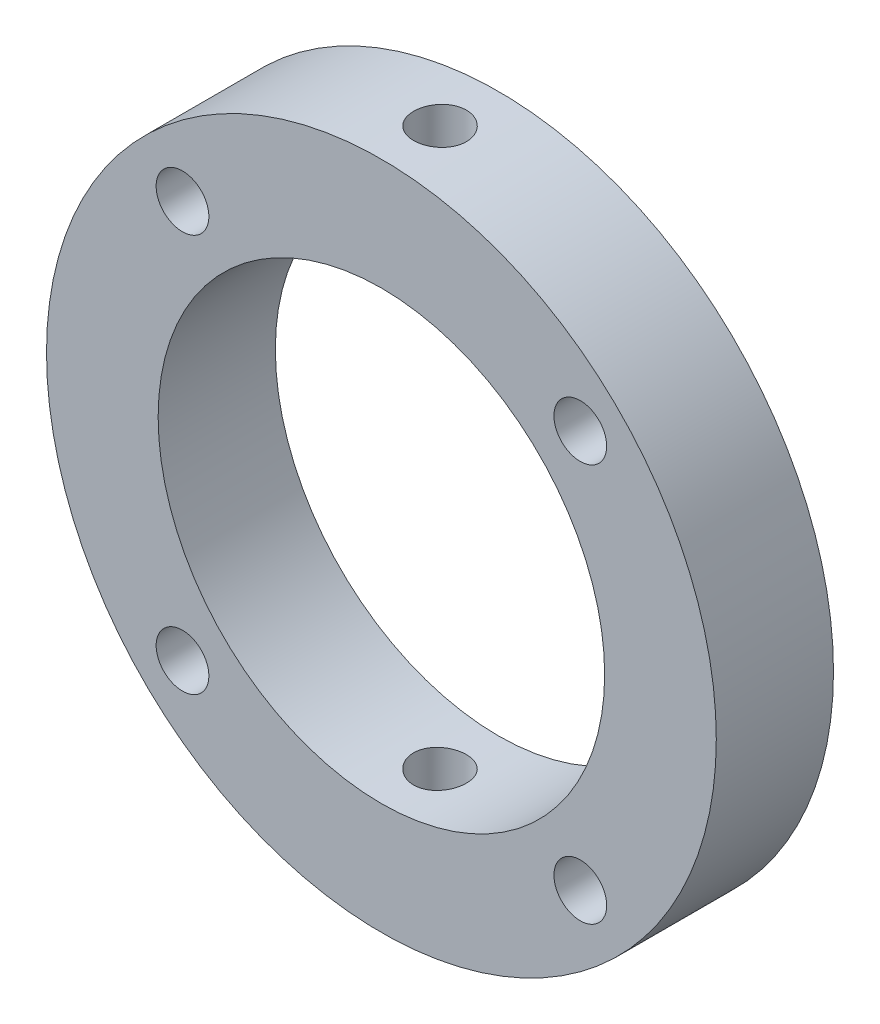
SolidWorks part; units mm, degrees
ref_plane "Front Plane" through (0, 0, 0) normal (0, 0, 1) x (1, 0, 0)
ref_plane "Top Plane" through (0, 0, 0) normal (0, 1, 0) x (1, 0, 0)
ref_plane "Right Plane" through (0, 0, 0) normal (1, 0, 0) x (0, 0, -1)
sketch "Sketch1" plane through (0, 0, 0) normal (0, 0, 1) x (1, 0, 0)
  circle A0 centre (0, 0) radius 28.575
  dimension "D1" = 57.15
extrude "Boss-Extrude1" add sketch "Sketch1" along normal blind 10
sketch "Sketch2" plane through (0, 0, 10) normal (0, 0, 1) x (1, 0, 0)
  circle A0 centre (0, 0) radius 19.05
  dimension "D1" = 38.1
extrude "Cut-Extrude1" cut sketch "Sketch2" against normal through all
ref_plane "Plane1" through (0, 28.575, 0) normal (0, 1, 0) x (1, 0, 0)
sketch "Sketch5" plane through (0, 28.575, 0) normal (0, 1, 0) x (1, 0, 0)
  circle A0 centre (0, -5) radius 2.25
  dimension "D2" = 4.5
  dimension "D1" = 5
extrude "Cut-Extrude2" cut sketch "Sketch5" against normal through all
sketch "Sketch6" plane through (0, 0, 10) normal (0, 0, 1) x (1, 0, 0)
  line L0 (0, 28.575) -> (0, -28.575) construction
  line L1 (5.5, 28.575) -> (-5.5, 28.575) construction
  line L2 (0, 0) -> (-16.9706, 16.9706) construction
  circle A1 centre (0, 0) radius 28.575 construction
  circle A3 centre (0, 0) radius 24 construction
  circle A4 centre (-16.9706, 16.9706) radius 2.25
  circle A5 centre (16.9706, 16.9706) radius 2.25
  circle A6 centre (16.9706, -16.9706) radius 2.25
  circle A7 centre (-16.9706, -16.9706) radius 2.25
  point P21 (0, 0)
  dimension "D2" = 45
  dimension "D1" = 48
  dimension "D3" = 4.5
  dimension "D4" = 4
extrude "Cut-Extrude3" cut sketch "Sketch6" against normal through all
ref_plane "Offset to Inner Ring" through (0, 18.575, 0) normal (0, 1, 0) x (1, 0, 0)
sketch "Sketch7" plane through (0, 28.575, 0) normal (0, 1, 0) x (1, 0, 0)
  circle A0 centre (0, -5) radius 4
  dimension "D1" = 8
